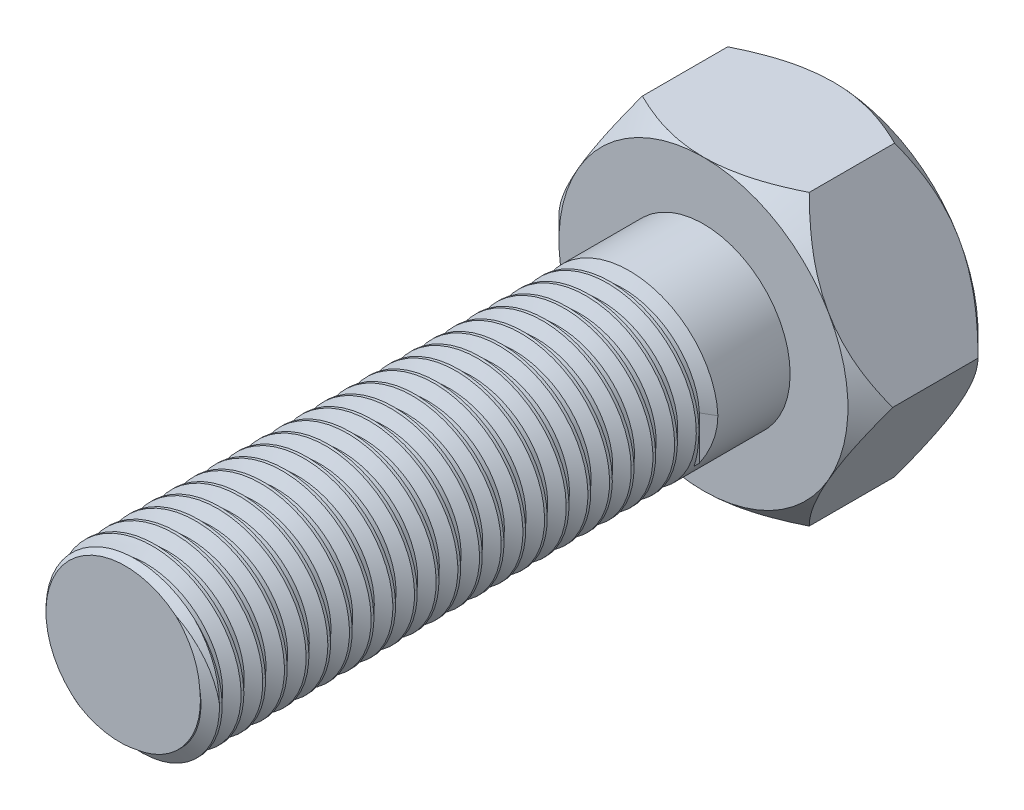
SolidWorks part; units mm, degrees
ref_plane "Front Plane" through (0, 0, 0) normal (0, 0, 1) x (1, 0, 0)
ref_plane "Top Plane" through (0, 0, 0) normal (0, 1, 0) x (1, 0, 0)
ref_plane "Right Plane" through (0, 0, 0) normal (1, 0, 0) x (0, 0, -1)
sketch "Sketch2" plane through (0, 0, 0) normal (0, 0, 1) x (1, 0, 0)
  line L1 (-11.547, 0) -> (-5.7735, -10)
  line L2 (-5.7735, -10) -> (5.7735, -10)
  line L3 (5.7735, -10) -> (11.547, 0)
  line L4 (11.547, 0) -> (5.7735, 10)
  line L5 (5.7735, 10) -> (-5.7735, 10)
  line L6 (-5.7735, 10) -> (-11.547, 0)
  circle A0 centre (0, 0) radius 10 construction
  dimension "D1" = 20
extrude "Boss-Extrude1" add sketch "Sketch2" along normal mid plane 9
sketch "Sketch3" plane through (0, 0, 4.5) normal (0, 0, 1) x (1, 0, 0)
  line L0 (-5.7735, 10) -> (-11.547, 0) construction
  circle A0 centre (0, 0) radius 10
extrude "Cut-Extrude1" cut sketch "Sketch3" against normal through all draft 45 flip side to cut
mirror "Mirror1" about plane through (0, 0, 0) normal (0, 0, 1) of "Cut-Extrude1"
sketch "Sketch4" plane through (0, 0, 4.5) normal (0, 0, 1) x (1, 0, 0)
  circle A0 centre (0, 0) radius 6
  dimension "D1" = 12
extrude "Boss-Extrude2" add sketch "Sketch4" along normal blind 40
chamfer "Chamfer1" distance 0.5 angle 45 1 edges at (6, 0, 44.5)
thread "Thread1" pitch 1.5 method cut profile "Thread Profile1" start angle 0, offset 5, length 0, pitch 1.5, diameter 12
ref_plane "Plane1" through (6, 0, 9.5) normal (0, -1, 0) x (1, 0, 0)
sketch "Thread Profile1" plane through (6, 0, 9.5) normal (0, -1, 0) x (1, 0, 0)
  line L0 (0, 0) -> (0, 1.5) construction
  line L11 (0, 0) -> (0, 1.3125)
  line L12 (0, 1.3125) -> (-0.8119, 0.8437)
  line L13 (-0.8119, 0.8437) -> (-0.8119, 0.4687)
  line L15 (-0.8119, 0.4687) -> (0, 0)
  line L17 (-0.8119, 0.6562) -> (0, 0.6562) construction
  point P2 (0, 0)
  dimension "Pitch" = 1.5
  dimension "Profile_Angle" = 60
  dimension "Profile_Land" = 0.375
  dimension "Profile_Height" = 0.8119
sketch "Sketch10" plane through (0, 0, 0) normal (0, 1, 0) x (1, 0, 0)
  line L4 (6, -9.5) -> (5.1881, -9.9687)
  line L5 (5.1881, -9.9687) -> (5.1881, -10.3437)
  line L6 (5.1881, -10.3437) -> (6, -10.8125)
  line L7 (6, -10.8125) -> (6, -9.5)
  line L8 (6, -9.5) -> (5.1881, -9.9687)
  line L9 (5.1881, -9.9687) -> (5.1881, -10.3437)
  line L10 (5.1881, -10.3437) -> (6, -10.8125)
  line L11 (6, -10.8125) -> (6, -9.5)
  dimension "D1" = 0
extrude "Cut-Extrude2" cut sketch "Sketch10" against normal through all
